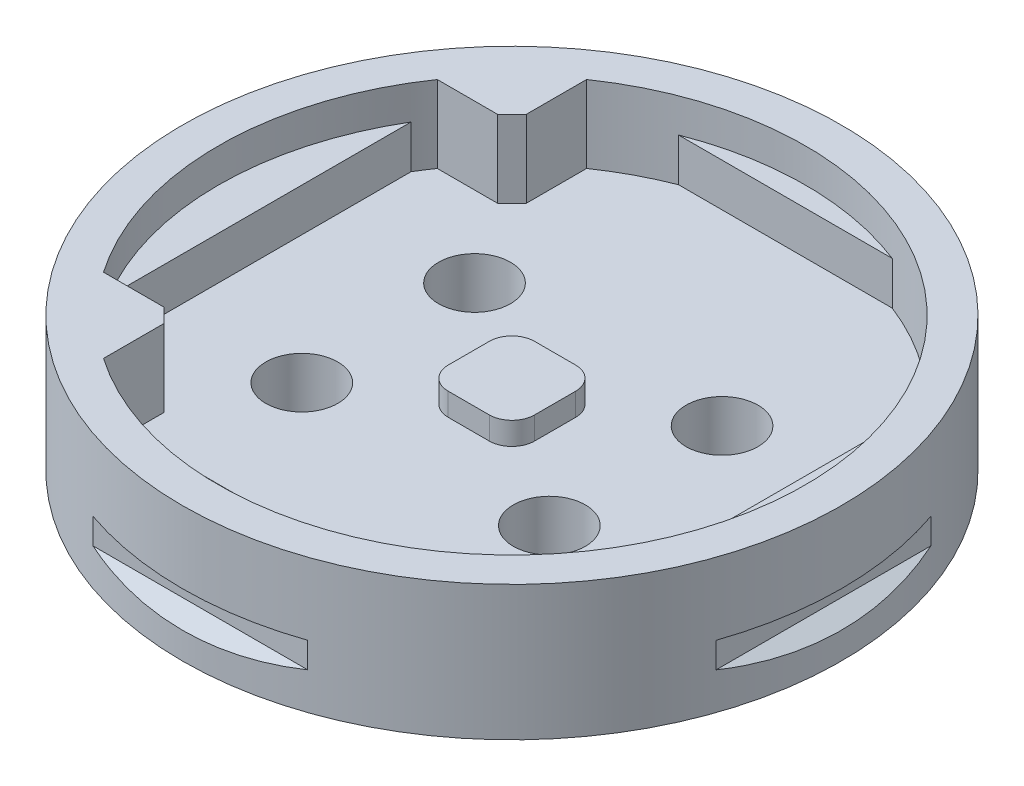
SolidWorks part; units mm, degrees
ref_plane "Front Plane" through (0, 0, 0) normal (0, 0, 1) x (1, 0, 0)
ref_plane "Top Plane" through (0, 0, 0) normal (0, 1, 0) x (1, 0, 0)
ref_plane "Right Plane" through (0, 0, 0) normal (1, 0, 0) x (0, 0, -1)
sketch "Sketch1" plane through (0, 0, 0) normal (0, 1, 0) x (1, 0, 0)
  line L0 (-11.1125, 6.6572) -> (-11.1125, -6.6572)
  line L1 (11.1125, 6.6572) -> (11.1125, -6.6572)
  line L2 (-6.096, -11.43) -> (6.096, -11.43)
  line L3 (-1.905, 1.905) -> (1.905, 1.905)
  line L4 (-1.905, 1.905) -> (-1.905, -1.905)
  line L5 (-1.905, -1.905) -> (1.905, -1.905)
  line L6 (1.905, 1.905) -> (1.905, -1.905)
  line L7 (-1.905, 1.905) -> (1.905, -1.905) construction
  line L8 (-1.905, -1.905) -> (1.905, 1.905) construction
  line L9 (-4.7161, 12.065) -> (4.7161, 12.065)
  line L11 (-5.461, 3.81) -> (5.461, 3.81) construction
  line L12 (-5.461, 3.81) -> (-5.461, -3.81) construction
  line L13 (-5.461, -3.81) -> (5.461, -3.81) construction
  line L14 (5.461, 3.81) -> (5.461, -3.81) construction
  circle A0 centre (0, 0) radius 14.5415
  arc A1 (-11.1125, -6.6572) -> (-6.096, -11.43) centre (0, 0) ccw
  arc A2 (11.1125, 6.6572) -> (4.7161, 12.065) centre (0, 0) ccw
  arc A3 (-4.7161, 12.065) -> (-11.1125, 6.6572) centre (0, 0) ccw
  arc A4 (6.096, -11.43) -> (11.1125, -6.6572) centre (0, 0) ccw
  circle A5 centre (0, 0) radius 1.5875
  circle A6 centre (-5.461, 3.81) radius 1.5875
  circle A7 centre (5.461, 3.81) radius 1.5875
  circle A8 centre (5.461, -3.81) radius 1.5875
  circle A9 centre (-5.461, -3.81) radius 1.5875
  point P15 (0, 12.065)
  point P16 (0, -11.43)
  point P22 (0, -3.81)
  point P23 (-5.461, 0)
  point P30 (1.9689, 4.8849)
  dimension "D1" = 25.908
  dimension "D2" = 1.5875
  dimension "D7" = 3.175
  dimension "D3" = 22.225
  dimension "D4" = 3.81
  dimension "D5" = 12.065
  dimension "D6" = 11.43
  dimension "D8" = 5.461
  dimension "D9" = 3.81
extrude "Boss-Extrude2" add sketch "Sketch1" along normal blind 2.54 contours A0
extrude "Boss-Extrude4" add sketch "Sketch1<8>" along normal blind 1 from surface contours L5 L6 L3 L4 starting at face at (0, 2.54, 14.5415)
sketch "Sketch1<8>" plane through (0, 0, 0) normal (0, 1, 0) x (1, 0, 0) same geometry as "Sketch1"
extrude "Boss-Extrude3" add sketch "Sketch1<6>" along normal offset from surface (1.9 mm away) 0.9 from surface contours A0 A4 L2 A1 L0 A3 L9 A2 L1 region at (-14.1302, 0, 0) up to face at (0, 3.54, 0) offset beyond the face yes starting at face at (0, 2.54, 14.5415)
sketch "Sketch1<6>" plane through (0, 0, 0) normal (0, 1, 0) x (1, 0, 0) same geometry as "Sketch1"
extrude "Cut-Extrude2" cut sketch "Sketch1<9>" along normal blind 3.175 contours A5 | A6 | A7 | A8 | A9 region at (0, 0, 0) region at (-5.461, 0, -3.81)
sketch "Sketch1<9>" plane through (0, 0, 0) normal (0, 1, 0) x (1, 0, 0) same geometry as "Sketch1"
sketch "Sketch2" plane through (0, 4.44, 0) normal (0, 1, 0) x (1, 0, 0)
  circle A3 centre (0, 0) radius 12.954
  circle A4 centre (0, 0) radius 14.5415
  circle A5 centre (0, 0) radius 14.5415 construction
  arc A6 (6.096, -11.43) -> (11.1125, -6.6572) centre (0, 0) ccw construction
extrude "Boss-Extrude5" add sketch "Sketch2" along normal blind 1.5 contours A3 region at (-14.1302, 4.44, 0)
sketch "Sketch3" plane through (0, 2.54, 0) normal (0, 1, 0) x (1, 0, 0)
  line L0 (-10.6574, 7.3638) -> (-7.3638, 7.3638)
  line L1 (-7.3638, 7.3638) -> (-7.3638, 10.6574)
  line L2 (0, 0) -> (-7.3638, 7.3638) construction
  line L4 (0, 0) -> (0, 7.5041) construction
  line L5 (0, 0) -> (-8.8822, 0) construction
  line L6 (-10.6574, -7.3638) -> (-7.3638, -7.3638)
  line L7 (-7.3638, -7.3638) -> (-7.3638, -10.6574)
  arc A0 (-4.7161, 12.065) -> (-11.1125, 6.6572) centre (0, 0) ccw construction
  arc A1 (-10.6574, 7.3638) -> (-7.3638, 10.6574) centre (0, 0) cw
  arc A2 (-10.6574, -7.3638) -> (-7.3638, -10.6574) centre (0, 0) ccw
  dimension "D1" = 45
  dimension "D2" = 10.414
extrude "Boss-Extrude6" add sketch "Sketch3" along normal up to surface (3.4 mm away) up to face at (0, 5.94, 12.954)
fillet "Fillet1" radius 1 4 edges at (1.905, 3.04, -1.905) (-1.905, 3.04, -1.905) (-1.905, 3.04, 1.905) (1.905, 3.04, 1.905)
chamfer "Chamfer1" distance 0.635 angle 45 2 edges at (-7.3638, 4.24, 7.3638) (-7.3638, 4.24, -7.3638)
sketch "Sketch4" plane through (0, 0, 0) normal (0, 0, 1) x (1, 0, 0)
  line L0 (-14.5415, 5.94) -> (-14.5415, 0) construction
  line L1 (-14.5415, 2.765) -> (-13.7478, 2.765)
  line L2 (-14.5415, 2.765) -> (-14.5415, 1.1775)
  line L3 (-14.5415, 1.1775) -> (-13.7478, 1.6358)
  line L4 (-13.7478, 2.765) -> (-13.7478, 1.6358)
  line L5 (-14.5415, 5.94) -> (-14.5415, 0) construction
  line L6 (14.5415, 5.94) -> (-14.5415, 5.94) construction
  point P8 (-14.5415, 1.1775)
  point P9 (-13.9329, 1.687)
  dimension "D1" = 3.175
  dimension "D2" = 1.5875
  dimension "D3" = 0.7937
  dimension "D4" = 60
extrude "Cut-Extrude3" cut sketch "Sketch4" against normal through all both and the other way through all
pattern_circular "CirPattern1" count 4 over 360 about axis through (0, 2.54, 0) along (0, -1, 0) of "Cut-Extrude3"
